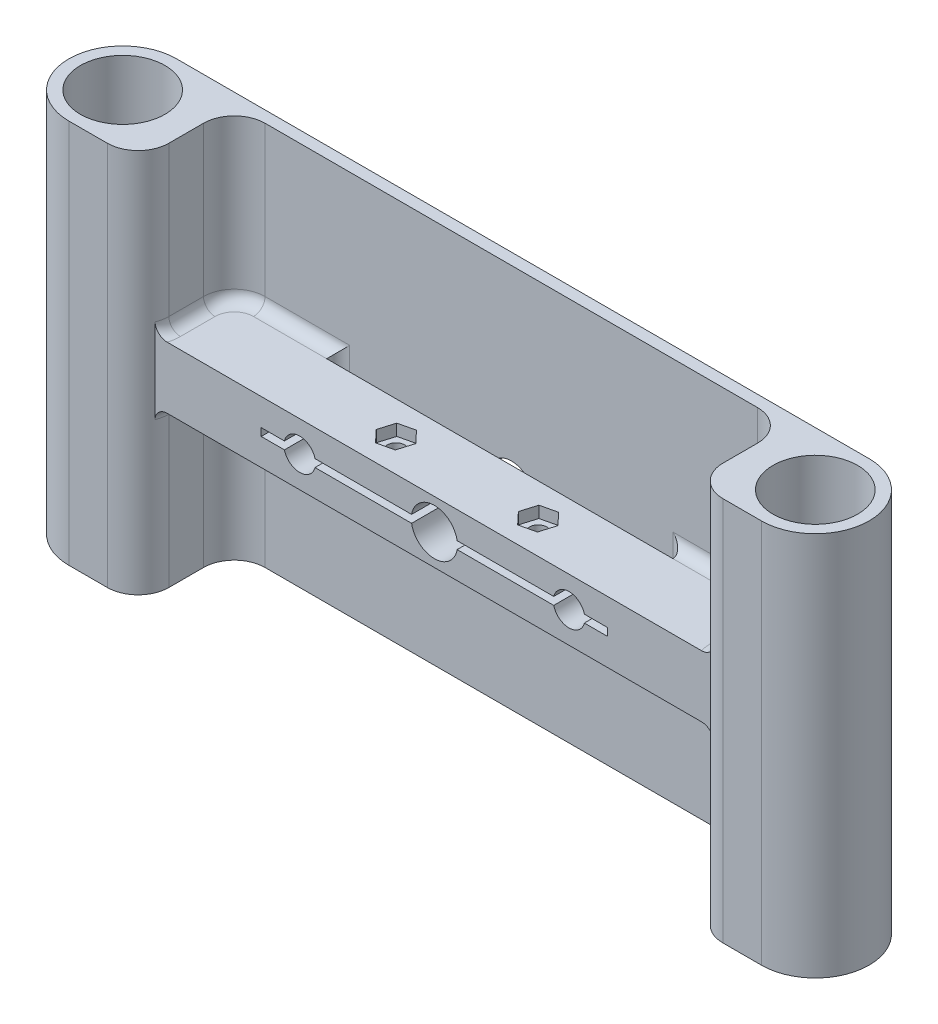
SolidWorks part; units mm, degrees
ref_plane "Front Plane" through (0, 0, 0) normal (0, 0, 1) x (1, 0, 0)
ref_plane "Top Plane" through (0, 0, 0) normal (0, 1, 0) x (1, 0, 0)
ref_plane "Right Plane" through (0, 0, 0) normal (1, 0, 0) x (0, 0, -1)
sketch "Sketch1" plane through (0, 0, 0) normal (0, 1, 0) x (1, 0, 0)
  line L0 (137.4606, -14.5) -> (119.4606, -14.5)
  line L1 (119.4606, -14.5) -> (119.4606, 10.5)
  line L2 (-42.5394, -14.5) -> (-24.5394, -14.5)
  line L3 (-42.5394, 13.5) -> (137.4606, 13.5)
  line L4 (119.4606, 10.5) -> (-24.5394, 10.5)
  line L5 (-24.5394, -14.5) -> (-24.5394, 10.5)
  circle A0 centre (-42.5394, -0.5) radius 11
  circle A1 centre (137.4606, -0.5) radius 11
  arc A2 (-42.5394, -14.5) -> (-42.5394, 13.5) centre (-42.5394, -0.5) cw
  arc A6 (137.4606, 13.5) -> (137.4606, -14.5) centre (137.4606, -0.5) cw
  dimension "D3" = 22
  dimension "D4" = 22
  dimension "D5" = 180
  dimension "D6" = 3
  dimension "D1" = 18
  dimension "D2" = 18
  dimension "D8" = 3
extrude "Boss-Extrude1" add sketch "Sketch1" along normal blind 100
fillet "Fillet1" radius 8 4 edges at (119.4606, 50, -10.5) (119.4606, 50, 14.5) (-24.5394, 50, -10.5) (-24.5394, 50, 14.5)
sketch "Sketch2" plane through (0, 0, -10.5) normal (0, 0, 1) x (1, 0, 0)
  line L0 (47.4606, 100) -> (47.4606, 0) construction
  line L1 (-16.5394, 100) -> (111.4606, 100) construction
  line L2 (-16.5394, 0) -> (111.4606, 0) construction
  circle A0 centre (12.4606, 50) radius 4.1
  circle A1 centre (82.4606, 50) radius 4.1
  circle A2 centre (47.4606, 50) radius 6
  point P10 (47.4606, 50)
  dimension "D1" = 8.2
  dimension "D2" = 8.2
  dimension "D5" = 12
  dimension "D3" = 35
  dimension "D4" = 35
extrude "Cut-Extrude1" cut sketch "Sketch2" against normal blind 10
sketch "Sketch3" plane through (0, 0, -10.5) normal (0, 0, 1) x (1, 0, 0)
  line L0 (12.4606, 58) -> (82.4606, 58)
  line L1 (12.4606, 42) -> (82.4606, 42)
  line L2 (12.4606, 58) -> (-16.5394, 58)
  line L3 (-16.5394, 100) -> (-16.5394, 0) construction
  line L4 (-16.5394, 58) -> (-28.8663, 58)
  line L5 (-28.8663, 58) -> (-28.8663, 42)
  line L6 (-28.8663, 42) -> (12.4606, 42)
  line L7 (82.4606, 58) -> (124.1494, 58)
  line L8 (124.1494, 58) -> (124.1494, 42)
  line L9 (124.1494, 42) -> (82.4606, 42)
  circle A2 centre (12.4606, 50) radius 4.1
  circle A3 centre (82.4606, 50) radius 4.1
  circle A4 centre (47.4606, 50) radius 6
  dimension "D2" = 12
extrude "Boss-Extrude2" add sketch "Sketch3" along normal blind 20
fillet "Fillet2" radius 3 14 edges at (-24.6867, 42, 8.0281) (-24.5394, 42, 2) (-22.1963, 42, -8.1569) (119.6079, 42, 8.0281) (119.4606, 42, 2) (117.1174, 42, -8.1569) (119.6079, 58, 8.0281) (119.4606, 58, 2) (-24.6867, 58, 8.0281) (-24.5394, 58, 2) (-22.1963, 58, -8.1569) (47.4606, 58, -10.5) (47.4606, 42, -10.5) (117.1174, 58, -8.1569)
sketch "Sketch4" plane through (0, 0, 9.5) normal (0, 0, 1) x (1, 0, 0)
  line L0 (47.4606, 50) -> (2.4606, 50)
  line L1 (47.4606, 50) -> (92.4606, 50)
  dimension "D1" = 45
extrude "Cut-Extrude-Thin1" cut sketch "Sketch4" against normal up to surface (20 mm away) and the other way through all thin up to face at (47.4606, 19.5, -10.5) thin type mid plane wall 2
sketch "Sketch5" plane through (0, 42, 0) normal (0, -1, 0) x (-1, 0, 0)
  line L0 (-2.4606, 7.5) -> (-47.4606, 7.5)
  line L1 (16.5394, 7.5) -> (-111.4606, 7.5) construction
  line L2 (-47.4606, 7.5) -> (-92.4606, 7.5)
  dimension "D1" = 45
  dimension "D2" = 45
extrude "Cut-Extrude-Thin2" cut sketch "Sketch5" against normal blind 20 and the other way through all thin thin type one direction wall 3
fillet "Fillet3" radius 3 2 edges at (92.4606, 50, -10.5) (2.4606, 50, -10.5)
sketch "Sketch6" plane through (0, 49, 0) normal (0, 1, 0) x (1, 0, 0)
  line L0 (16.4368, 7.5) -> (41.5445, -9.5) construction
  line L1 (41.5445, -9.5) -> (53.3767, -9.5) construction
  line L2 (53.3767, -9.5) -> (78.4844, 7.5) construction
  circle A0 centre (28.9906, -1) radius 2.25
  circle A1 centre (65.9305, -1) radius 2.25
  dimension "D1" = 4.5
  dimension "D2" = 4.5
extrude "Cut-Extrude2" cut sketch "Sketch6" against normal through all both and the other way through all
sketch "Sketch7" plane through (0, 58, 0) normal (0, 1, 0) x (1, 0, 0)
  line L1 (33.1506, -0.0263) -> (30.2274, 3.0895)
  line L2 (30.2274, 3.0895) -> (26.0674, 2.1158)
  line L3 (26.0674, 2.1158) -> (24.8307, -1.9737)
  line L4 (24.8307, -1.9737) -> (27.7539, -5.0895)
  line L5 (27.7539, -5.0895) -> (31.9138, -4.1158)
  line L6 (31.9138, -4.1158) -> (33.1506, -0.0263)
  line L7 (70.0905, -0.0263) -> (67.1673, 3.0895)
  line L8 (67.1673, 3.0895) -> (63.0073, 2.1158)
  line L9 (63.0073, 2.1158) -> (61.7706, -1.9737)
  line L10 (61.7706, -1.9737) -> (64.6938, -5.0895)
  line L11 (64.6938, -5.0895) -> (68.8537, -4.1158)
  line L12 (68.8537, -4.1158) -> (70.0905, -0.0263)
  circle A0 centre (28.9906, -1) radius 3.7 construction
  circle A1 centre (65.9305, -1) radius 3.7 construction
  dimension "D1" = 7.4
  dimension "D2" = 7.4
extrude "Cut-Extrude3" cut sketch "Sketch7" against normal blind 3
